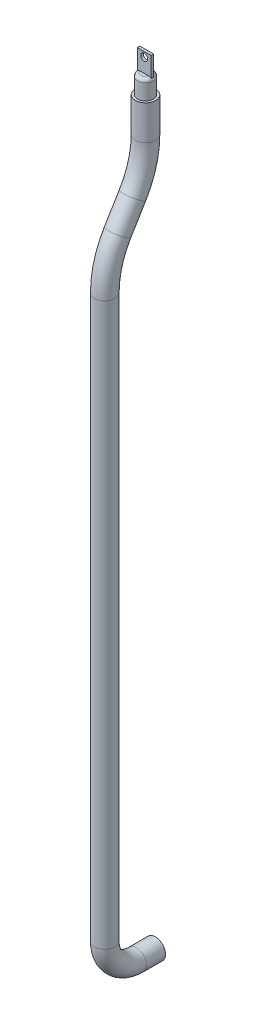
SolidWorks part; units mm, degrees
ref_plane "Alzado" through (0, 0, 0) normal (0, 0, 1) x (1, 0, 0)
ref_plane "Planta" through (0, 0, 0) normal (0, 1, 0) x (1, 0, 0)
ref_plane "Vista lateral" through (0, 0, 0) normal (1, 0, 0) x (0, 0, -1)
sketch3d "Croquis3D1"
  line L0 (1505.09, -551.24, 2179.521) -> (1505.09, -605.8393, 2179.521)
  line L2 (1505.09, -678.527, 2199.8695) -> (1505.09, -717.4669, 2223.5253)
  line L3 (1505.09, -790.1546, 2243.8737) -> (1505.09, -1677.6153, 2243.8737)
  line L4 (1505.09, -1727.6153, 2193.8737) -> (1505.09, -1727.6153, 2163.8737)
  arc A0 (1505.09, -717.4669, 2223.5253) -> (1505.09, -790.1546, 2243.8737) centre (1505.09, -790.1546, 2103.8737) ccw
  arc A1 (1505.09, -605.8393, 2179.521) -> (1505.09, -678.527, 2199.8695) centre (1505.09, -605.8393, 2319.521) ccw
  arc A2 (1505.09, -1677.6153, 2243.8737) -> (1505.09, -1727.6153, 2193.8737) centre (1505.09, -1677.6153, 2193.8737) ccw
  point P10 (1505.09, -750.9626, 2243.8737)
  point P11 (1645.09, -790.1546, 2103.8737)
  point P14 (1505.09, -645.0313, 2179.521)
  point P15 (1365.09, -605.8393, 2319.521)
  point P18 (1505.09, -1727.6153, 2243.8737)
  point P19 (1555.09, -1677.6153, 2193.8737)
  dimension "D1" = 140
  dimension "D2" = 50
  dimension "D3" = 80
sweep "Barrer1" add path "Croquis3D1" circular profile diameter 32 parameters "D3"=32
sketch "Croquis13" plane through (0, -551.24, 0) normal (0, 1, 0) x (1, 0, 0)
  circle A0 centre (1505.09, -2179.521) radius 12.4625
extrude "Saliente-Extruir1" add sketch "Croquis13" along normal blind 30
sketch "Croquis14" plane through (0, -521.24, 0) normal (0, 1, 0) x (1, 0, 0)
  line L0 (1492.6275, -2179.521) -> (1517.5525, -2179.521) construction
  circle A0 centre (1505.09, -2179.521) radius 12.4625 construction
  circle A1 centre (1505.09, -2179.521) radius 12.4625 construction
ref_plane "Plano1" through (0, 0, 2179.521) normal (0, 0, 1) x (1, 0, 0)
sketch "Croquis15" plane through (0, 0, 2179.521) normal (0, 0, 1) x (1, 0, 0)
  line L0 (1505.09, -521.24) -> (1505.09, -482.5469) construction
  line L1 (1516.09, -491.24) -> (1494.09, -491.24)
  line L2 (1516.09, -491.24) -> (1516.09, -521.24)
  line L3 (1516.09, -521.24) -> (1494.09, -521.24)
  line L4 (1494.09, -491.24) -> (1494.09, -521.24)
  line L5 (1516.09, -491.24) -> (1494.09, -521.24) construction
  line L6 (1516.09, -521.24) -> (1494.09, -491.24) construction
  line L7 (1492.6275, -521.24) -> (1517.5525, -521.24) construction
  circle A0 centre (1505.09, -499.0052) radius 5.5
  point P8 (1505.09, -506.24)
  dimension "D3" = 11
  dimension "D1" = 30
  dimension "D2" = 22
extrude "Saliente-Extruir2" add sketch "Croquis15" along normal blind 2 and the other way blind 2
fillet "Redondeo1" radius 5 1 edges at (1505.09, -521.24, 2191.9835)
